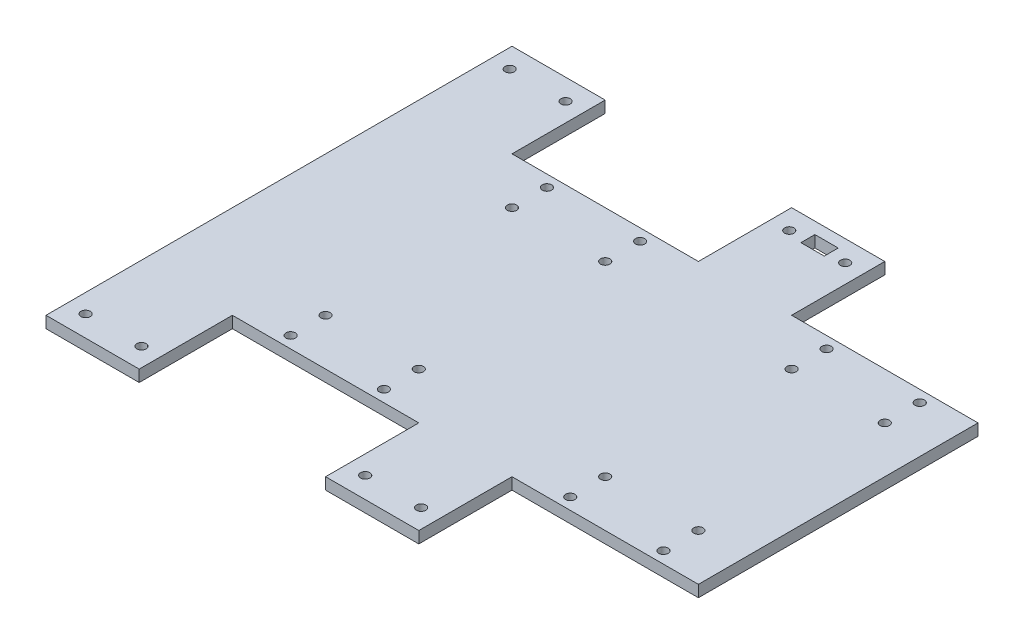
SolidWorks part; units mm, degrees
ref_plane "Front Plane" through (0, 0, 0) normal (0, 0, 1) x (1, 0, 0)
ref_plane "Top Plane" through (0, 0, 0) normal (0, 1, 0) x (1, 0, 0)
ref_plane "Right Plane" through (0, 0, 0) normal (1, 0, 0) x (0, 0, -1)
sketch "Sketch1" plane through (0, 0, 0) normal (0, 1, 0) x (1, 0, 0)
  line L0 (0, 0) -> (0, 152.4) construction
  line L13 (0, 152.4) -> (101.6, 152.4)
  line L16 (152.4, 152.4) -> (254, 152.4)
  line L17 (254, 152.4) -> (254, 0)
  line L18 (254, 0) -> (152.4, 0)
  line L21 (101.6, 0) -> (0, 0)
  line L22 (101.6, 152.4) -> (101.6, 203.2)
  line L23 (101.6, 203.2) -> (152.4, 203.2)
  line L24 (152.4, 203.2) -> (152.4, 152.4)
  line L25 (101.6, 0) -> (101.6, -50.8)
  line L26 (101.6, -50.8) -> (152.4, -50.8)
  line L27 (152.4, -50.8) -> (152.4, 0)
  line L28 (0, 152.4) -> (0, 203.2)
  line L29 (0, 203.2) -> (-50.8, 203.2)
  line L30 (-50.8, 203.2) -> (-50.8, -50.8)
  line L31 (-50.8, -50.8) -> (0, -50.8)
  line L32 (0, -50.8) -> (0, 0)
  point P18 (0, 0)
  point P19 (0, 0)
  point P20 (0, 0)
  dimension "D1" = 254
  dimension "D2" = 152.4
  dimension "D3" = 101.6
  dimension "D4" = 50.8
  dimension "D5" = 50.8
  dimension "D6" = 50.8
  dimension "D7" = 50.8
extrude "Boss-Extrude1" add sketch "Sketch1" along normal blind 6.35
sketch "Sketch2" plane through (0, 6.35, 0) normal (0, 1, 0) x (1, 0, 0)
  line L0 (152.4, 203.2) -> (101.6, 203.2) construction
  line L1 (133.35, 189.23) -> (120.65, 189.23)
  line L2 (133.35, 189.23) -> (133.35, 196.85)
  line L3 (133.35, 196.85) -> (120.65, 196.85)
  line L4 (120.65, 189.23) -> (120.65, 196.85)
  point P6 (127, 203.2)
  dimension "D1" = 12.7
  dimension "D2" = 7.62
  dimension "D3" = 6.35
  dimension "D4" = 19.05
extrude "Cut-Extrude1" cut sketch "Sketch2" against normal through all contours L2 L3 L4 L1
sketch "Sketch3" plane through (0, 0, 0) normal (0, -1, 0) x (1, 0, 0)
  line L0 (0, -76.2) -> (254, -76.2) construction
  line L2 (254, 0) -> (254, -152.4) construction
  line L3 (254, -152.4) -> (152.4, -152.4) construction
  line L4 (101.6, 50.8) -> (152.4, 50.8) construction
  line L5 (127, 50.8) -> (127, -203.2) construction
  line L6 (152.4, -203.2) -> (101.6, -203.2) construction
  line L7 (0, 0) -> (0, -152.4) construction
  line L8 (50.8, 0) -> (50.8, -152.4) construction
  line L9 (0, 0) -> (101.6, 0) construction
  line L10 (101.6, -152.4) -> (0, -152.4) construction
  circle A0 centre (228.6, -146.05) radius 2.54
  circle A1 centre (177.8, -146.05) radius 2.54
  circle A2 centre (228.6, -127) radius 2.54
  circle A3 centre (177.8, -127) radius 2.54
  circle A4 centre (177.8, -25.4) radius 2.54
  circle A5 centre (228.6, -25.4) radius 2.54
  circle A6 centre (177.8, -6.35) radius 2.54
  circle A7 centre (228.6, -6.35) radius 2.54
  circle A8 centre (25.4, -6.35) radius 2.54
  circle A9 centre (76.2, -6.35) radius 2.54
  circle A10 centre (25.4, -25.4) radius 2.54
  circle A11 centre (76.2, -25.4) radius 2.54
  circle A12 centre (76.2, -127) radius 2.54
  circle A13 centre (25.4, -127) radius 2.54
  circle A14 centre (76.2, -146.05) radius 2.54
  circle A15 centre (25.4, -146.05) radius 2.54
  circle A16 centre (142.24, -191.77) radius 2.54
  circle A17 centre (111.76, -191.77) radius 2.54
  circle A18 centre (142.24, 39.37) radius 2.54
  circle A19 centre (111.76, 39.37) radius 2.54
  circle A20 centre (-10.16, 39.37) radius 2.54
  circle A21 centre (-40.64, 39.37) radius 2.54
  circle A22 centre (-10.16, -191.77) radius 2.54
  circle A23 centre (-40.64, -191.77) radius 2.54
  point P15 (0, -76.2)
  dimension "D1" = 5.08
  dimension "D4" = 5.08
  dimension "D6" = 15.24
  dimension "D2" = 50.8
  dimension "D3" = 25.4
  dimension "D5" = 6.35
  dimension "D7" = 19.05
  dimension "D8" = 11.43
extrude "Cut-Extrude2" cut sketch "Sketch3" against normal through all
